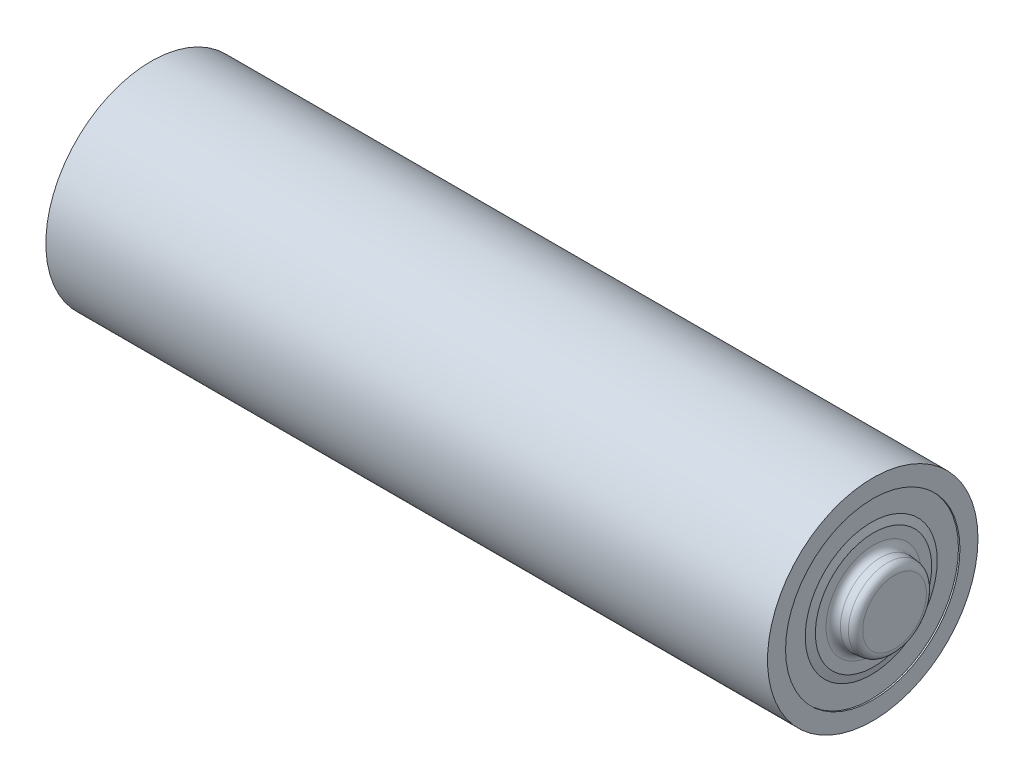
SolidWorks part; units mm, degrees
ref_plane "Front Plane" through (0, 0, 0) normal (0, 0, 1) x (1, 0, 0)
ref_plane "Top Plane" through (0, 0, 0) normal (0, 1, 0) x (1, 0, 0)
ref_plane "Right Plane" through (0, 0, 0) normal (1, 0, 0) x (0, 0, -1)
sketch "Sketch1" plane through (0, 0, 0) normal (1, 0, 0) x (0, 0, -1)
  circle A0 centre (0, 0) radius 7
extrude "Boss-Extrude1" add sketch "Sketch1" along normal blind 48
sketch "Sketch2" plane through (48, 0, 0) normal (1, 0, 0) x (0, 0, -1)
  circle A2 centre (0, 0) radius 5.8
  circle A3 centre (0, 0) radius 5.8
  dimension "D1" = 1.2
extrude "Cut-Extrude1" cut sketch "Sketch2" against normal blind 0.1
sketch "Sketch3" plane through (0, 0, 0) normal (-1, 0, 0) x (0, 0, 1)
  circle A2 centre (0, 0) radius 5.25
  circle A3 centre (0, 0) radius 5.25
  dimension "D1" = 1.75
extrude "Cut-Extrude2" cut sketch "Sketch3" against normal blind 0.1
sketch "Sketch4" plane through (0.1, 0, 0) normal (-1, 0, 0) x (0, 0, 1)
  circle A1 centre (0, 0) radius 3.45
  circle A2 centre (0, 0) radius 5.05
  circle A3 centre (0, 0) radius 5.05
  dimension "D1" = 0.2
  dimension "D2" = 1.6
extrude "Boss-Extrude2" add sketch "Sketch4" along normal blind 0.1
fillet "Fillet1" radius 0.5 2 edges at (0, 0, 3.45) (0, 0, 5.05)
sketch "Sketch5" plane through (0.1, 0, 0) normal (-1, 0, 0) x (0, 0, 1)
  circle A2 centre (0, 0) radius 3.35
  circle A3 centre (0, 0) radius 3.35
  dimension "D1" = 0.1
extrude "Boss-Extrude3" add sketch "Sketch5" along normal blind 0.1 draft 46
fillet "Fillet4" radius 0.1 3 edges at (0.1, 0, 3.45) (0.1, 0, 3.35) (0, 0, 3.2464)
sketch "Sketch6" plane through (47.9, 0, 0) normal (1, 0, 0) x (0, 0, -1)
  circle A0 centre (0, 0) radius 4.39
extrude "Boss-Extrude4" add sketch "Sketch6" along normal blind 0.15 draft 74
sketch "Sketch7" plane through (48.05, 0, 0) normal (1, 0, 0) x (0, 0, -1)
  circle A0 centre (0, 0) radius 2.7
extrude "Boss-Extrude5" add sketch "Sketch7" along normal blind 1.4 draft 5
fillet "Fillet5" radius 0.5 1 edges at (48.05, 0, -2.7)
fillet "Fillet6" radius 0.5 1 edges at (49.45, 0, -2.5775)
